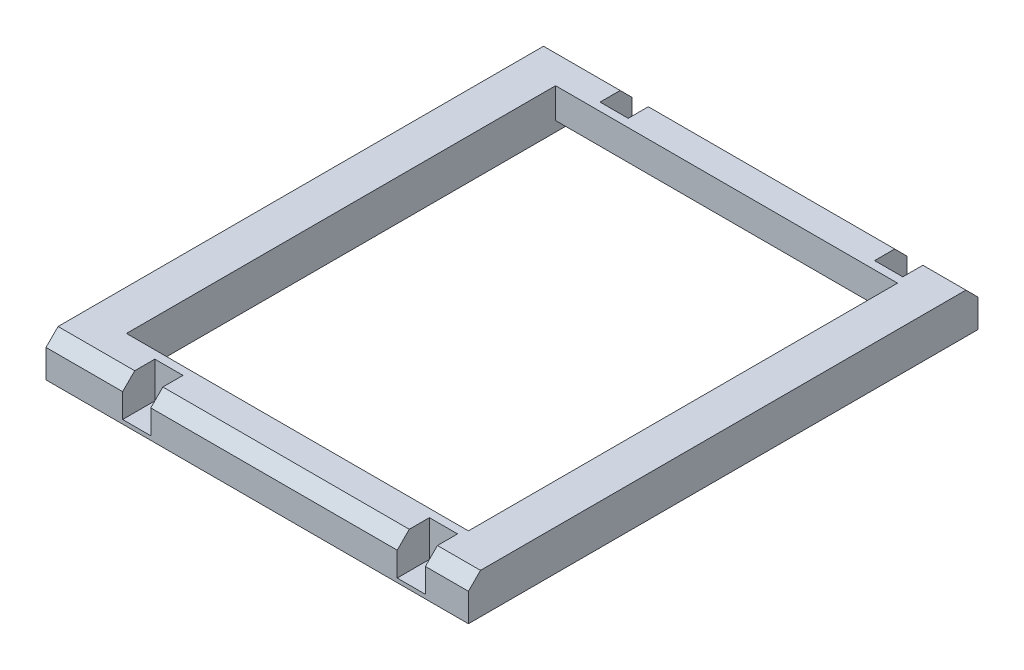
SolidWorks part; units mm, degrees
ref_plane "Front Plane" through (0, 0, 0) normal (0, 0, 1) x (1, 0, 0)
ref_plane "Top Plane" through (0, 0, 0) normal (0, 1, 0) x (1, 0, 0)
ref_plane "Right Plane" through (0, 0, 0) normal (1, 0, 0) x (0, 0, -1)
sketch "Sketch2" plane through (0, 0, 0) normal (0, 1, 0) x (1, 0, 0)
  line L1 (-66.675, -80.4333) -> (66.675, -80.4333)
  line L2 (-66.675, -80.4333) -> (-66.675, 80.4333)
  line L3 (-66.675, 80.4333) -> (66.675, 80.4333)
  line L4 (66.675, -80.4333) -> (66.675, 80.4333)
  line L5 (53.975, -67.7333) -> (-53.975, -67.7333)
  line L6 (53.975, -67.7333) -> (53.975, 67.7333)
  line L7 (53.975, 67.7333) -> (-53.975, 67.7333)
  line L8 (-53.975, -67.7333) -> (-53.975, 67.7333)
  point P4 (-66.675, 0)
  point P9 (0, -80.4333)
  point P11 (53.975, 0)
  point P12 (0, -67.7333)
  dimension "D1" = 12.7
  dimension "D2" = 12.7
  dimension "D3" = 160.8667
  dimension "D4" = 133.35
extrude "Boss-Extrude1" add sketch "Sketch2" along normal blind 12.7
sketch "Sketch4" plane through (0, 0, 0) normal (0, 1, 0) x (1, 0, 0)
  line L0 (-63.5, 76.2) -> (-60.325, 79.375)
  line L1 (-63.5, 76.2) -> (-60.325, 73.025)
  line L2 (-60.325, 79.375) -> (-57.15, 76.2)
  line L3 (-60.325, 73.025) -> (-57.15, 76.2)
  line L4 (-63.5, 76.2) -> (-57.15, 76.2) construction
  line L5 (-60.325, 79.375) -> (-60.325, 73.025) construction
  line L6 (-52.9167, 76.2) -> (-49.7417, 79.375)
  line L7 (-52.9167, 76.2) -> (-49.7417, 73.025)
  line L8 (-49.7417, 79.375) -> (-46.5667, 76.2)
  line L9 (-49.7417, 73.025) -> (-46.5667, 76.2)
  line L10 (-52.9167, 76.2) -> (-46.5667, 76.2) construction
  line L11 (-49.7417, 79.375) -> (-49.7417, 73.025) construction
  line L12 (57.15, 76.2) -> (60.325, 79.375)
  line L13 (57.15, 76.2) -> (60.325, 73.025)
  line L14 (60.325, 79.375) -> (63.5, 76.2)
  line L15 (60.325, 73.025) -> (63.5, 76.2)
  line L16 (57.15, 76.2) -> (63.5, 76.2) construction
  line L17 (60.325, 79.375) -> (60.325, 73.025) construction
  line L18 (57.15, -76.2) -> (60.325, -73.025)
  line L19 (57.15, -76.2) -> (60.325, -79.375)
  line L20 (60.325, -73.025) -> (63.5, -76.2)
  line L21 (60.325, -79.375) -> (63.5, -76.2)
  line L22 (57.15, -76.2) -> (63.5, -76.2) construction
  line L23 (60.325, -73.025) -> (60.325, -79.375) construction
  line L24 (-52.9167, -76.2) -> (-49.7417, -73.025)
  line L25 (-52.9167, -76.2) -> (-49.7417, -79.375)
  line L26 (-49.7417, -73.025) -> (-46.5667, -76.2)
  line L27 (-49.7417, -79.375) -> (-46.5667, -76.2)
  line L28 (-52.9167, -76.2) -> (-46.5667, -76.2) construction
  line L29 (-49.7417, -73.025) -> (-49.7417, -79.375) construction
  line L30 (-63.5, -76.2) -> (-60.325, -73.025)
  line L31 (-63.5, -76.2) -> (-60.325, -79.375)
  line L32 (-60.325, -73.025) -> (-57.15, -76.2)
  line L33 (-60.325, -79.375) -> (-57.15, -76.2)
  line L34 (-63.5, -76.2) -> (-57.15, -76.2) construction
  line L35 (-60.325, -73.025) -> (-60.325, -79.375) construction
  line L36 (-66.675, 80.4333) -> (-66.675, -80.4333) construction
  line L37 (66.675, 80.4333) -> (-66.675, 80.4333) construction
  line L38 (66.675, -80.4333) -> (66.675, 80.4333) construction
  line L39 (-66.675, -80.4333) -> (66.675, -80.4333) construction
  point P1 (-60.325, 76.2)
  point P2 (-49.7417, 76.2)
  point P3 (60.325, 76.2)
  point P8 (60.325, -76.2)
  point P13 (-49.7417, -76.2)
  point P18 (-60.325, -76.2)
  dimension "D1" = 6.35
  dimension "D2" = 4.2333
  dimension "D3" = 6.35
  dimension "D4" = 10.5833
  dimension "D5" = 6.35
  dimension "D6" = 4.2333
extrude "Cut-Extrude1" cut sketch "Sketch4" along normal blind 6.35
chamfer "Chamfer1" distance 0.635 angle 45 50 edges at (-61.9125, 6.35, -77.7875) (-58.7375, 6.35, -77.7875) (-58.7375, 6.35, -74.6125) (-61.9125, 6.35, -74.6125) (-51.3292, 6.35, -77.7875) (-48.1542, 6.35, -77.7875) (-48.1542, 6.35, -74.6125) (-51.3292, 6.35, -74.6125) (58.7375, 6.35, -77.7875) (61.9125, 6.35, -77.7875) (61.9125, 6.35, -74.6125) (58.7375, 6.35, -74.6125) (58.7375, 6.35, 74.6125) (61.9125, 6.35, 74.6125) (61.9125, 6.35, 77.7875) (58.7375, 6.35, 77.7875) (-51.3292, 6.35, 74.6125) (-48.1542, 6.35, 74.6125) (-48.1542, 6.35, 77.7875) (-51.3292, 6.35, 77.7875) (-61.9125, 6.35, 74.6125) (-58.7375, 6.35, 74.6125) (-58.7375, 6.35, 77.7875) (-61.9125, 6.35, 77.7875) (-61.9125, 0, -77.7875) (-61.9125, 0, -74.6125) (-58.7375, 0, -74.6125) (-58.7375, 0, -77.7875) (-51.3292, 0, -77.7875) (-48.1542, 0, -77.7875) (-48.1542, 0, -74.6125) (-51.3292, 0, -74.6125) (58.7375, 0, -77.7875) (61.9125, 0, -77.7875) (61.9125, 0, -74.6125) (58.7375, 0, -74.6125) (61.9125, 0, 74.6125) (61.9125, 0, 77.7875) (58.7375, 0, 77.7875) (58.7375, 0, 74.6125) (-52.9167, 3.175, 76.2) (-49.7417, 3.175, 73.025) (-51.3292, 0, 74.6125) (-48.1542, 0, 74.6125) (-48.1542, 0, 77.7875) (-51.3292, 0, 77.7875) (-61.9125, 0, 74.6125) (-58.7375, 0, 74.6125) (-58.7375, 0, 77.7875) (-61.9125, 0, 77.7875)
chamfer "Chamfer3" distance 3.81 angle 45 2 edges at (0, 12.7, 80.4333) (0, 12.7, -80.4333)
sketch "Sketch5" plane through (0, 0, 80.4333) normal (0, 0, 1) x (1, 0, 0)
  line L0 (-66.675, 12.7) -> (66.675, 12.7) construction
  line L1 (-42.4815, 1.27) -> (-33.5915, 1.27)
  line L2 (-42.4815, 1.27) -> (-42.4815, 12.7)
  line L3 (-42.4815, 12.7) -> (-33.5915, 12.7)
  line L4 (-33.5915, 1.27) -> (-33.5915, 12.7)
  line L5 (-66.675, 8.89) -> (-66.675, 0) construction
  line L6 (44.196, 1.27) -> (53.086, 1.27)
  line L7 (44.196, 1.27) -> (44.196, 12.7)
  line L8 (44.196, 12.7) -> (53.086, 12.7)
  line L9 (53.086, 1.27) -> (53.086, 12.7)
  dimension "D1" = 8.89
  dimension "D2" = 8.89
  dimension "D3" = 24.1935
  dimension "D4" = 77.7875
  dimension "D5" = 11.43
extrude "Cut-Extrude2" cut sketch "Sketch5" against normal offset from surface (10.16 mm away) 2.54 up to face at (0, 6.35, 67.7333)
sketch "Sketch6" plane through (0, 0, -80.4333) normal (0, 0, -1) x (-1, 0, 0)
  line L1 (42.4815, 1.27) -> (33.5915, 1.27)
  line L2 (42.4815, 1.27) -> (42.4815, 12.7)
  line L3 (42.4815, 12.7) -> (33.5915, 12.7)
  line L4 (33.5915, 1.27) -> (33.5915, 12.7)
  line L5 (-44.196, 1.27) -> (-53.086, 1.27)
  line L6 (-44.196, 1.27) -> (-44.196, 12.7)
  line L7 (-44.196, 12.7) -> (-53.086, 12.7)
  line L8 (-53.086, 1.27) -> (-53.086, 12.7)
extrude "Cut-Extrude3" cut sketch "Sketch6" against normal offset from surface (10.16 mm away) 2.54 up to face at (0, 6.35, -67.7333)
chamfer "Chamfer4" distance 3.175 angle 45 2 edges at (0, 0, 67.7333) (0, 0, -67.7333)
